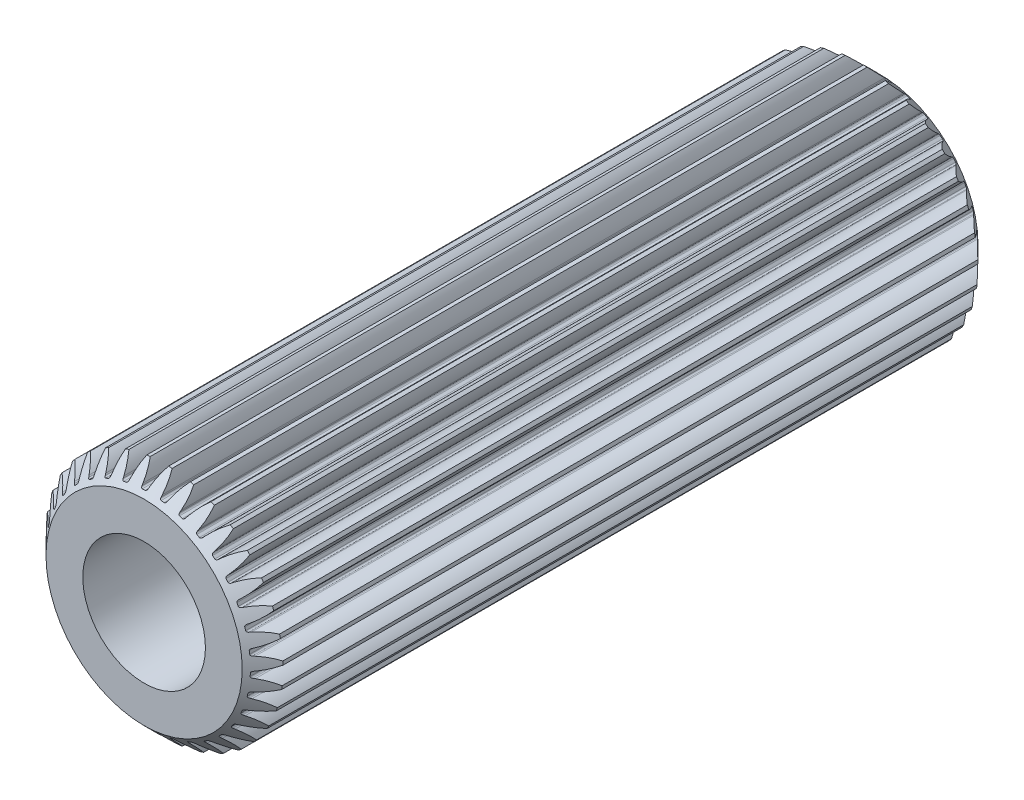
SolidWorks part; units mm, degrees
ref_plane "Piano frontale" through (0, 0, 0) normal (0, 0, 1) x (1, 0, 0)
ref_plane "Piano superiore" through (0, 0, 0) normal (0, 1, 0) x (1, 0, 0)
ref_plane "Piano destro" through (0, 0, 0) normal (1, 0, 0) x (0, 0, -1)
sketch "Schizzo3" plane through (0, 0, 0) normal (0, 0, 1) x (1, 0, 0)
  circle A0 centre (0, 0) radius 2.9
  dimension "D1" = 5.8
extrude "Estrusione-Estrusione2" add sketch "Schizzo3" along normal blind 18
chamfer "Smusso2" distance 0.5 angle 45 2 edges at (2.9, 0, 0) (2.9, 0, 18)
sketch "Schizzo4" plane through (0, 0, 18) normal (0, 0, 1) x (1, 0, 0)
  line L0 (0, 0) -> (2.9, 0) construction
  line L1 (2.73, 0) -> (2.73, -0.9783) construction
  line L2 (2.8731, -0.3942) -> (2.4103, 0.8773) construction
  line L3 (2.5646, -0.0436) -> (2.5318, -0.0491)
  line L4 (0, 0) -> (2.8965, -0.1423) construction
  line L5 (2.5566, -0.208) -> (2.5245, -0.1993)
  circle A0 centre (0, 0) radius 2.9 construction
  arc A1 (2.8769, -0.3653) -> (2.8989, 0.0816) centre (0, 0) ccw
  circle A2 centre (0, 0) radius 2.73 construction
  arc A3 (2.495, -0.1582) -> (2.4985, -0.0871) centre (0, 0) ccw
  circle A4 centre (0, 0) radius 2.565 construction
  arc A5 (2.8989, 0.0816) -> (2.5646, -0.0436) centre (2.4103, 0.8773) cw
  arc A6 (2.8769, -0.3653) -> (2.5566, -0.208) centre (2.3127, -1.1093) ccw
  arc A7 (2.5318, -0.0491) -> (2.4985, -0.0871) centre (2.5385, -0.0885) ccw
  arc A8 (2.5245, -0.1993) -> (2.495, -0.1582) centre (2.5349, -0.1607) cw
  point P22 (2.4994, -0.0545)
  point P25 (2.4927, -0.1907)
  dimension "D1" = 5.46
  dimension "D2" = 5
  dimension "D3" = 5.13
  dimension "D4" = 5.8
  dimension "D7" = 0.04
  dimension "D8" = 0.04
  dimension "D5" = 20
  dimension "D6" = 2.813
extrude "Taglio-Estrusione1" cut sketch "Schizzo4" against normal blind 18
pattern_circular "RipetizioneCircolare1" count 34 over 360 about axis through (0, 0, 18) along (0, 0, 1) of "Taglio-Estrusione1"
sketch "Schizzo6" plane through (0, 0, 18) normal (0, 0, 1) x (1, 0, 0)
  circle A0 centre (0, 0) radius 1.5
  dimension "D1" = 3
extrude "Taglio-Estrusione2" cut sketch "Schizzo6" against normal blind 9
